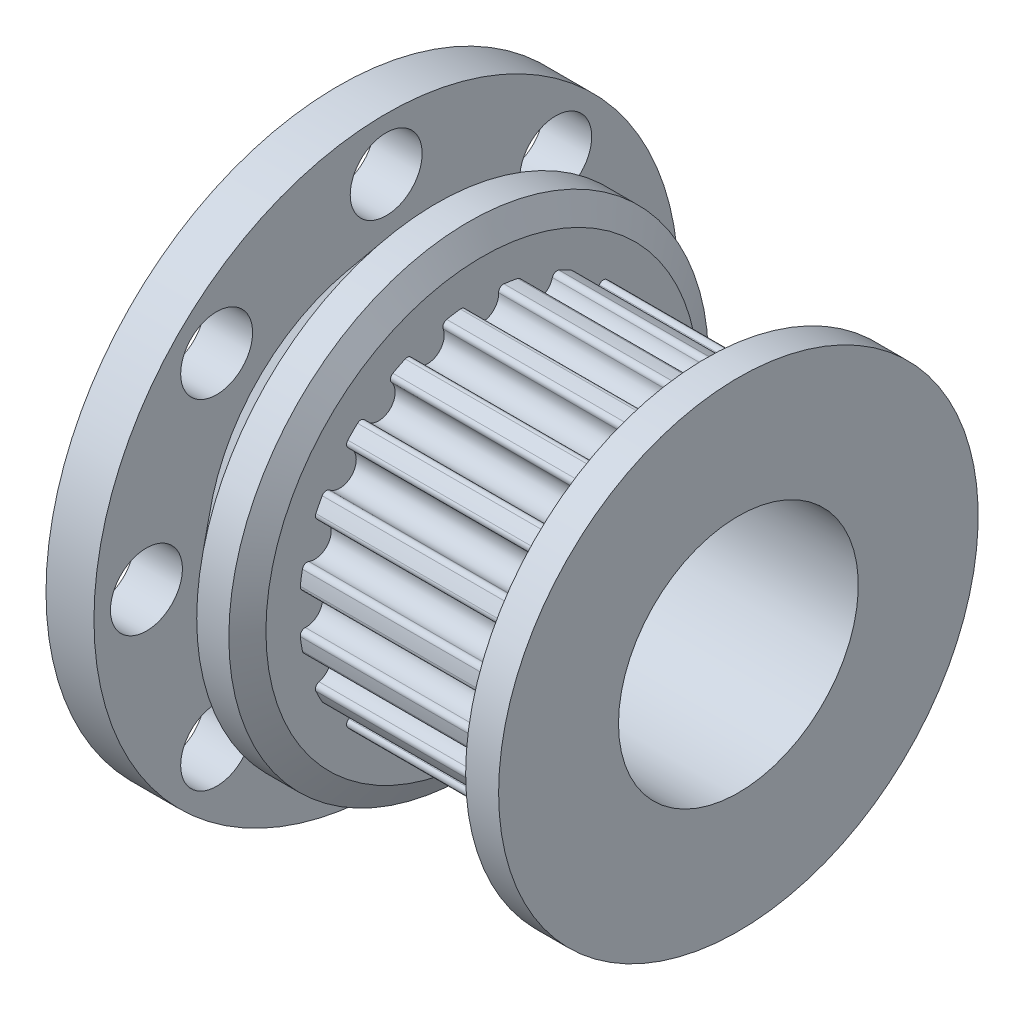
SolidWorks part; units mm, degrees
note: '?' marks a value the reader was unsure of.
other "Main_Body" parameters "D16"=0.5
material "6061-O (SS)"
ref_plane "Сверху" through (0, 0, 0) normal (0, 0, 1) x (1, 0, 0)
ref_plane "Справа" through (0, 0, 0) normal (0, 1, 0) x (1, 0, 0)
ref_plane "Спереди" through (0, 0, 0) normal (1, 0, 0) x (0, 0, -1)
sketch "Эскиз1" plane through (0, 0, 0) normal (0, 0, 1) x (1, 0, 0)
  line L0 (0, 0) -> (0, 6)
  line L1 (1.6782, 8) -> (0, 6)
  line L2 (1.6782, 8) -> (2.7497, 8)
  line L3 (2.7497, 8) -> (3.2, 7.2132)
  line L4 (3.2, 6.11) -> (10.2, 6.11)
  line L5 (10.2, 6.11) -> (10.2, 7.2132)
  line L6 (10.6503, 8) -> (11.75, 8)
  line L7 (11.75, 0) -> (11.75, 4.2314)
  line L8 (11.75, 4.2314) -> (11.5975, 4.3838)
  line L9 (11.5975, 4.3838) -> (11.75, 4.5363)
  line L10 (11.75, 4.5363) -> (11.75, 8)
  line L11 (0, 0) -> (11.75, 0)
  line L12 (3.2, 7.2132) -> (3.2, 6.11)
  line L13 (10.2, 7.2132) -> (10.6503, 8)
  dimension "D2" = 50
  dimension "D3" = 6
  dimension "D5" = 3.2
  dimension "D6" = 6.11
  dimension "D7" = 11.75
  dimension "D8" = 7
  dimension "D9" = 0.9066
  dimension "D10" = 0.2156
  dimension "D11" = 8
  dimension "D12" = 1.1032
  dimension "D13" = 3.4637
revolve "Body" add sketch "Эскиз1" angle 360 about L11
sketch "Эскиз2" plane through (11.75, 0, 0) normal (1, 0, 0) x (0, 0, -1)
  circle A0 centre (0, 0) radius 3.175
  dimension "D1" = 6.35
extrude "Bore" cut sketch "Эскиз2" against normal through all
sketch "Эскиз3" plane through (3.2, 0, 0) normal (1, 0, 0) x (0, 0, -1)
  line L0 (0, 0) -> (9.7637, 0) construction
  circle A0 centre (5.5827, -1.8139) radius 0.55
  circle A1 centre (0, 0) radius 6.42 construction
  circle A2 centre (4.7489, -3.4503) radius 0.55
  circle A3 centre (3.4503, -4.7489) radius 0.55
  circle A4 centre (1.8139, -5.5827) radius 0.55
  circle A5 centre (0, -5.87) radius 0.55
  circle A6 centre (5.87, 0) radius 0.55
  circle A7 centre (-1.8139, -5.5827) radius 0.55
  circle A8 centre (-3.4503, -4.7489) radius 0.55
  circle A9 centre (-4.7489, -3.4503) radius 0.55
  circle A10 centre (-5.5827, -1.8139) radius 0.55
  circle A11 centre (-5.87, 0) radius 0.55
  circle A12 centre (-5.5827, 1.8139) radius 0.55
  circle A13 centre (-4.7489, 3.4503) radius 0.55
  circle A14 centre (-3.4503, 4.7489) radius 0.55
  circle A17 centre (-1.8139, 5.5827) radius 0.55
  circle A18 centre (0, 5.87) radius 0.55
  circle A19 centre (1.8139, 5.5827) radius 0.55
  circle A20 centre (3.4503, 4.7489) radius 0.55
  circle A21 centre (4.7489, 3.4503) radius 0.55
  circle A22 centre (5.5827, 1.8139) radius 0.55
  point P45 (0, 0)
  dimension "D1" = 12.84
  dimension "D2" = 20
  dimension "D3" = 1.1
extrude "20T" cut sketch "Эскиз3" along normal blind 7
fillet "Fillet" radius 0.16 40 edges at (6.7, 0.5045, -6.0891) (6.7, -0.5045, -6.0891) (6.7, -1.4019, -5.947) (6.7, -2.3614, -5.6352) (6.7, -3.171, -5.2227) (6.7, -3.9872, -4.6297) (6.7, -4.6297, -3.9872) (6.7, -5.2227, -3.171) (6.7, -5.6352, -2.3614) (6.7, -5.947, -1.4019) (6.7, -6.0891, -0.5045) (6.7, -6.0891, 0.5045) (6.7, -5.947, 1.4019) (6.7, -5.6352, 2.3614) (6.7, -5.2227, 3.171) (6.7, -4.6297, 3.9872) (6.7, -3.9872, 4.6297) (6.7, -3.171, 5.2227) (6.7, -2.3614, 5.6352) (6.7, -1.4019, 5.947) (6.7, -0.5045, 6.0891) (6.7, 0.5045, 6.0891) (6.7, 1.4019, 5.947) (6.7, 2.3614, 5.6352) (6.7, 3.171, 5.2227) (6.7, 3.9872, 4.6297) (6.7, 4.6297, 3.9872) (6.7, 5.2227, 3.171) (6.7, 5.6352, 2.3614) (6.7, 5.947, 1.4019) (6.7, 6.0891, 0.5045) (6.7, 6.0891, -0.5045) (6.7, 5.947, -1.4019) (6.7, 5.6352, -2.3614) (6.7, 5.2227, -3.171) (6.7, 4.6297, -3.9872) (6.7, 3.9872, -4.6297) (6.7, 3.171, -5.2227) (6.7, 2.3614, -5.6352) (6.7, 1.4019, -5.947)
ref_axis "Axis1" through (0, 0, 0) along (1, 0, 0)?
sketch "Sketch4" plane through (0, 0, 0) normal (-1, 0, 0) x (0, 0, 1)
  circle A0 centre (0, 0) radius 9.75
extrude "Boss-Extrude3" add sketch "Sketch4" along normal blind 1.6
sketch "Sketch5" plane through (-1.6, 0, 0) normal (-1, 0, 0) x (0, 0, 1)
  circle A0 centre (0, 0) radius 4
  dimension "D1" = 8
extrude "Cut-Extrude3" cut sketch "Sketch5" against normal through all
sketch "Sketch11" plane through (-1.6, 0, 0) normal (-1, 0, 0) x (0, 0, 1)
  line L0 (0, 0) -> (8, 0) construction
  circle A0 centre (8, 0) radius 1.2
  dimension "D2" = 2.4
  dimension "D1" = 8
extrude "Cut-Extrude4" cut sketch "Sketch11" against normal up to next
pattern_circular "CirPattern1" count 8 every 45 about axis through (0, 0, 0) along (1, 0, 0) of "Cut-Extrude4"
sketch "Sketch12" plane through (11.75, 0, 0) normal (1, 0, 0) x (0, 0, -1)
  circle A0 centre (0, 0) radius 4.5363 construction
  circle A1 centre (0, 0) radius 4.5363
  circle A2 centre (0, 0) radius 4.2314 construction
  circle A3 centre (0, 0) radius 4.2314
extrude "Boss-Extrude4" add sketch "Sketch12" against normal up to surface (0.3049 mm away) contours A1
